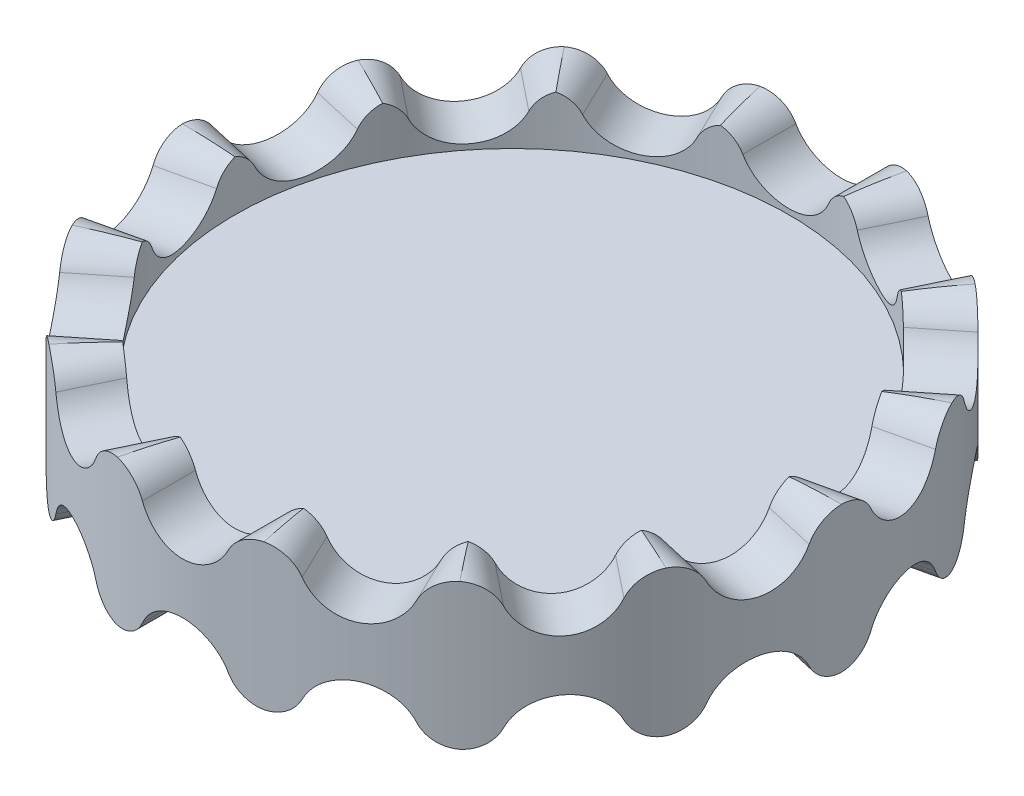
SolidWorks part; units mm, degrees
ref_plane "Front Plane" through (0, 0, 0) normal (0, 0, 1) x (1, 0, 0)
ref_plane "Top Plane" through (0, 0, 0) normal (0, 1, 0) x (1, 0, 0)
ref_plane "Right Plane" through (0, 0, 0) normal (1, 0, 0) x (0, 0, -1)
sketch "Sketch1" plane through (0, 0, 0) normal (0, 1, 0) x (1, 0, 0)
  circle A0 centre (0, 0) radius 15.9385
  dimension "D1" = 31.877
extrude "Boss-Extrude1" add sketch "Sketch1" along normal mid plane 7.0358
sketch "Sketch2" plane through (0, 3.5179, 0) normal (0, 1, 0) x (1, 0, 0)
  circle A0 centre (0, 0) radius 13.3985
  circle A1 centre (0, 0) radius 15.9385 construction
  dimension "D1" = 2.54
extrude "Cut-Extrude1" cut sketch "Sketch2" against normal blind 2.54
sketch "Sketch3" plane through (0, -3.5179, 0) normal (0, -1, 0) x (-1, 0, 0)
  circle A0 centre (0, 0) radius 13.3985
  circle A1 centre (0, 0) radius 15.9385 construction
  dimension "D1" = 2.54
extrude "Cut-Extrude2" cut sketch "Sketch3" against normal blind 2.54
sketch "Sketch5" plane through (0, 0, 0) normal (0, 0, 1) x (1, 0, 0)
  line L0 (15.9385, 3.5179) -> (-15.9385, 3.5179) construction
  line L1 (2.0905, 10.8651) -> (0.8635, 10.3197)
  circle A0 centre (0, 3.5179) radius 2.286
  dimension "D1" = 4.572
extrude "Cut-Extrude3" cut sketch "Sketch5" against normal through all both and the other way through all contours A0
pattern_circular "CirPattern5" count 7 over 360 about axis through (0, 3.5179, 0) along (0, -1, 0) of "Cut-Extrude3"
fillet "Fillet3" radius 1.6688 84 edges at (-2.9814, 3.5179, -13.0626) (-0.2488, 1.2455, -13.3962) (0.2488, 1.2455, 13.3962) (3.5466, 3.5179, 15.5389) (-3.5466, 3.5179, -15.5389) (-0.2534, 1.246, 15.9365) (0.2534, 1.246, -15.9365) (2.286, 3.5179, 14.4879) (-2.286, 3.5179, 14.4879) (-2.286, 3.5179, -14.4879) (2.286, 3.5179, -14.4879) (-8.3538, 3.5179, -10.4754) (-12.0716, 3.5179, -5.8134) (-13.3985, 3.5179, 0) (-12.0716, 3.5179, 5.8134) (-8.3538, 3.5179, 10.4754) (-2.9814, 3.5179, 13.0626) (8.3538, 3.5179, 10.4754) (12.0716, 3.5179, 5.8134) (13.3985, 3.5179, 0) (12.0716, 3.5179, -5.8134) (8.3538, 3.5179, -10.4754) (2.9814, 3.5179, -13.0626) (-13.1157, 1.2455, -2.7384) (-13.005, 1.2455, 3.2235) (-10.6287, 1.2455, -8.1579) (5.5882, 1.2455, -12.1775) (-6.0365, 1.2455, -11.9616) (-10.3184, 1.2455, 8.5469) (-5.5882, 1.2455, 12.1775) (6.0365, 1.2455, 11.9616) (10.6287, 1.2455, 8.1579) (13.005, 1.2455, -3.2235) (13.1157, 1.2455, 2.7384) (10.3184, 1.2455, -8.5469) (9.9375, 3.5179, 12.4612) (14.3601, 3.5179, 6.9155) (15.9385, 3.5179, 0) (14.3601, 3.5179, -6.9155) (9.9375, 3.5179, -12.4612) (3.5466, 3.5179, -15.5389) (-9.9375, 3.5179, -12.4612) (-14.3601, 3.5179, -6.9155) (-15.9385, 3.5179, 0) (-14.3601, 3.5179, 6.9155) (-9.9375, 3.5179, 12.4612) (-3.5466, 3.5179, 15.5389) (2.9814, 3.5179, 13.0626) (12.4535, 1.2319, -9.9471) (15.4171, 5.746, 4.0432) (15.4171, 1.2898, -4.0432) (12.4535, 5.8039, 9.9471) (6.9266, 1.2319, 14.3547) (-7.3725, 5.746, 14.1309) (-12.1361, 1.2898, 10.332) (-6.9043, 5.8039, -14.3654) (6.4513, 1.2898, -14.5745) (-12.4689, 1.2319, -9.9278) (-15.6446, 5.746, 3.0465) (-15.6446, 1.2898, -3.0465) (9.9018, 3.5179, -10.8203) (12.7524, 3.5179, -7.2458) (14.6333, 3.5179, 0.9952) (13.616, 3.5179, 5.4525) (13.616, 3.5179, -5.4525) (14.6333, 3.5179, -0.9952) (12.7524, 3.5179, 7.2458) (9.9018, 3.5179, 10.8203) (8.3457, 3.5179, 12.0613) (4.2264, 3.5179, 14.045) (-4.2264, 3.5179, 14.045) (-8.3457, 3.5179, 12.0613) (-9.9018, 3.5179, 10.8203) (-12.7524, 3.5179, 7.2458) (-8.3457, 3.5179, -12.0613) (-4.2264, 3.5179, -14.045) (4.2264, 3.5179, -14.045) (8.3457, 3.5179, -12.0613) (-12.7524, 3.5179, -7.2458) (-9.9018, 3.5179, -10.8203) (-13.616, 3.5179, 5.4525) (-14.6333, 3.5179, 0.9952) (-14.6333, 3.5179, -0.9952) (-13.616, 3.5179, -5.4525)
sketch "Sketch6" plane through (0, 0, 0) normal (0, 0, 1) x (1, 0, 0)
  line L0 (-15.9385, -3.5179) -> (15.9385, -3.5179) construction
  circle A0 centre (0, -3.5179) radius 2.286
  dimension "D1" = 4.572
extrude "Cut-Extrude4" cut sketch "Sketch6" against normal through all both and the other way through all
pattern_circular "CirPattern6" count 7 over 360 about axis through (0, 3.5179, 0) along (0, -1, 0) of "Cut-Extrude4"
fillet "Fillet4" radius 1.6688 84 edges at (2.9814, -3.5179, -13.0626) (-2.9814, -3.5179, 13.0626) (0.2488, -1.2455, -13.3962) (-0.2488, -1.2455, 13.3962) (3.5466, -3.5179, 15.5389) (-3.5466, -3.5179, -15.5389) (-2.286, -3.5179, 14.4879) (0.2534, -1.246, 15.9365) (2.286, -3.5179, 14.4879) (2.286, -3.5179, -14.4879) (-0.2534, -1.246, -15.9365) (-2.286, -3.5179, -14.4879) (8.3538, -3.5179, -10.4754) (12.0716, -3.5179, -5.8134) (13.3985, -3.5179, 0) (12.0716, -3.5179, 5.8134) (8.3538, -3.5179, 10.4754) (2.9814, -3.5179, 13.0626) (-8.3538, -3.5179, 10.4754) (-12.0716, -3.5179, 5.8134) (-13.3985, -3.5179, 0) (-12.0716, -3.5179, -5.8134) (-8.3538, -3.5179, -10.4754) (-2.9814, -3.5179, -13.0626) (-13.005, -1.2455, -3.2235) (-13.1157, -1.2455, 2.7384) (-10.3184, -1.2455, -8.5469) (6.0365, -1.2455, -11.9616) (-5.5882, -1.2455, -12.1775) (-10.6287, -1.2455, 8.1579) (-6.0365, -1.2455, 11.9616) (5.5882, -1.2455, 12.1775) (10.3184, -1.2455, 8.5469) (13.1157, -1.2455, -2.7384) (13.005, -1.2455, 3.2235) (10.6287, -1.2455, -8.1579) (9.9375, -3.5179, 12.4612) (14.3601, -3.5179, 6.9155) (15.9385, -3.5179, 0) (14.3601, -3.5179, -6.9155) (9.9375, -3.5179, -12.4612) (3.5466, -3.5179, -15.5389) (-9.9375, -3.5179, -12.4612) (-14.3601, -3.5179, -6.9155) (-15.9385, -3.5179, 0) (-14.3601, -3.5179, 6.9155) (-9.9375, -3.5179, 12.4612) (-3.5466, -3.5179, 15.5389) (12.7524, -3.5179, -7.2458) (12.4535, -5.8039, -9.9471) (9.9018, -3.5179, -10.8203) (13.616, -3.5179, 5.4525) (15.5416, -5.8039, 3.5346) (14.6333, -3.5179, 0.9952) (14.6333, -3.5179, -0.9952) (15.4171, -5.746, -4.0432) (13.616, -3.5179, -5.4525) (9.9018, -3.5179, 10.8203) (12.7735, -5.746, 9.5327) (12.7524, -3.5179, 7.2458) (4.2264, -3.5179, 14.045) (6.9266, -5.8039, 14.3547) (8.3457, -3.5179, 12.0613) (-8.3457, -3.5179, 12.0613) (-7.3725, -1.2898, 14.1309) (-4.2264, -3.5179, 14.045) (-12.7524, -3.5179, 7.2458) (-12.1361, -5.746, 10.332) (-9.9018, -3.5179, 10.8203) (-4.2264, -3.5179, -14.045) (-6.9043, -1.2319, -14.3654) (-8.3457, -3.5179, -12.0613) (8.3457, -3.5179, -12.0613) (6.4513, -5.746, -14.5745) (4.2264, -3.5179, -14.045) (-9.9018, -3.5179, -10.8203) (-12.4689, -5.8039, -9.9278) (-12.7524, -3.5179, -7.2458) (-14.6333, -3.5179, 0.9952) (-15.6446, -1.2898, 3.0465) (-13.616, -3.5179, 5.4525) (-13.616, -3.5179, -5.4525) (-15.6446, -5.746, -3.0465) (-14.6333, -3.5179, -0.9952)
